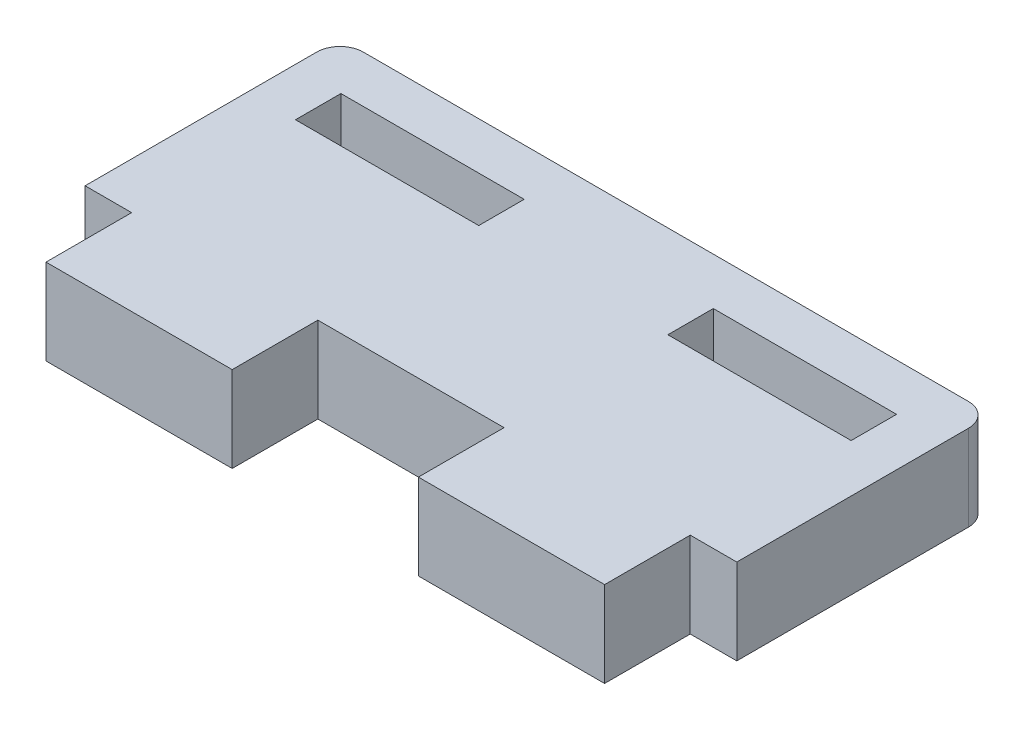
SolidWorks part; units mm, degrees
ref_plane "Front Plane" through (0, 0, 0) normal (0, 0, 1) x (1, 0, 0)
ref_plane "Top Plane" through (0, 0, 0) normal (0, 1, 0) x (1, 0, 0)
ref_plane "Right Plane" through (0, 0, 0) normal (1, 0, 0) x (0, 0, -1)
sketch "Sketch1" plane through (0, 0, 0) normal (0, 1, 0) x (1, 0, 0)
  line L0 (0, 4.7625) -> (0, -4.7625) construction
  line L1 (22.225, -6.35) -> (19.05, -6.35)
  line L2 (22.225, -6.35) -> (22.225, 6.35)
  line L3 (18.95, 4.7244) -> (6.45, 4.7244)
  line L4 (-22.225, -6.35) -> (-22.225, 6.35)
  line L5 (22.225, -6.35) -> (-22.225, 6.35) construction
  line L6 (22.225, 6.35) -> (-22.225, -6.35) construction
  line L7 (-6.35, -12.192) -> (-19.05, -12.192)
  line L8 (-6.35, -12.192) -> (-6.35, -6.35)
  line L9 (6.35, -6.35) -> (-6.35, -6.35)
  line L10 (-19.05, -12.192) -> (-19.05, -6.35)
  line L11 (-6.35, -12.192) -> (-19.05, -6.35) construction
  line L12 (-6.35, -6.35) -> (-19.05, -12.192) construction
  line L13 (-6.45, 7.8232) -> (-18.95, 7.8232)
  line L14 (6.45, 7.8232) -> (6.45, 4.7244)
  line L15 (6.35, -12.192) -> (6.35, -6.35)
  line L16 (-6.45, 7.8232) -> (-6.45, 4.7244)
  line L17 (6.45, 7.8232) -> (-6.45, 4.7244) construction
  line L18 (6.45, 4.7244) -> (-6.45, 7.8232) construction
  line L19 (18.95, 4.7244) -> (18.95, 7.8232)
  line L20 (-6.45, 4.7244) -> (-18.95, 4.7244)
  line L21 (-22.225, 6.35) -> (-22.225, 9.4488)
  line L22 (19.05, -12.192) -> (19.05, -6.35)
  line L23 (-18.95, 4.7244) -> (-18.95, 7.8232)
  line L24 (6.35, -12.192) -> (19.05, -12.192)
  line L25 (22.225, 6.35) -> (22.225, 9.4488)
  line L26 (22.225, 11.0363) -> (-22.225, 11.0363)
  line L27 (22.225, 11.0363) -> (22.225, 9.4488)
  line L28 (18.95, 7.8232) -> (6.45, 7.8232)
  line L29 (-22.225, 11.0363) -> (-22.225, 9.4488)
  line L30 (22.225, 11.0363) -> (-22.225, 9.4488) construction
  line L31 (22.225, 9.4488) -> (-22.225, 11.0363) construction
  line L32 (-19.05, -6.35) -> (-22.225, -6.35)
  point P0 (0, 0)
  point P6 (-12.7, -9.271)
  point P11 (0, 6.2738)
  point P24 (0, 10.2426)
  dimension "D1" = 44.45
  dimension "D2" = 12.7
  dimension "D3" = 3.0988
  dimension "D4" = 12.9
  dimension "D5" = 3.0988
  dimension "D6" = 4.7625
  dimension "D7" = 1.5875
  dimension "D8" = 5.842
  dimension "D9" = 12.7
  dimension "D10" = 12.7
extrude "Boss-Extrude1" add sketch "Sketch1" along normal blind 5.842
fillet "Fillet1" radius 1.5875 2 edges at (22.225, 2.921, -11.0363) (-22.225, 2.921, -11.0363)
sketch "Sketch2" [suppressed] plane through (0, 5.842, 0) normal (0, 1, 0) x (1, 0, 0)
  line L1 (6.35, -6.35) -> (19.05, -6.35)
  line L2 (6.35, -6.35) -> (6.35, -12.192)
  line L3 (6.35, -12.192) -> (19.05, -12.192)
  line L4 (19.05, -6.35) -> (19.05, -12.192)
  line L5 (6.35, -6.35) -> (19.05, -12.192) construction
  line L6 (6.35, -12.192) -> (19.05, -6.35) construction
  point P4 (12.7, -9.271)
extrude "Cut-Extrude1" [suppressed] cut sketch "Sketch2" against normal through all
